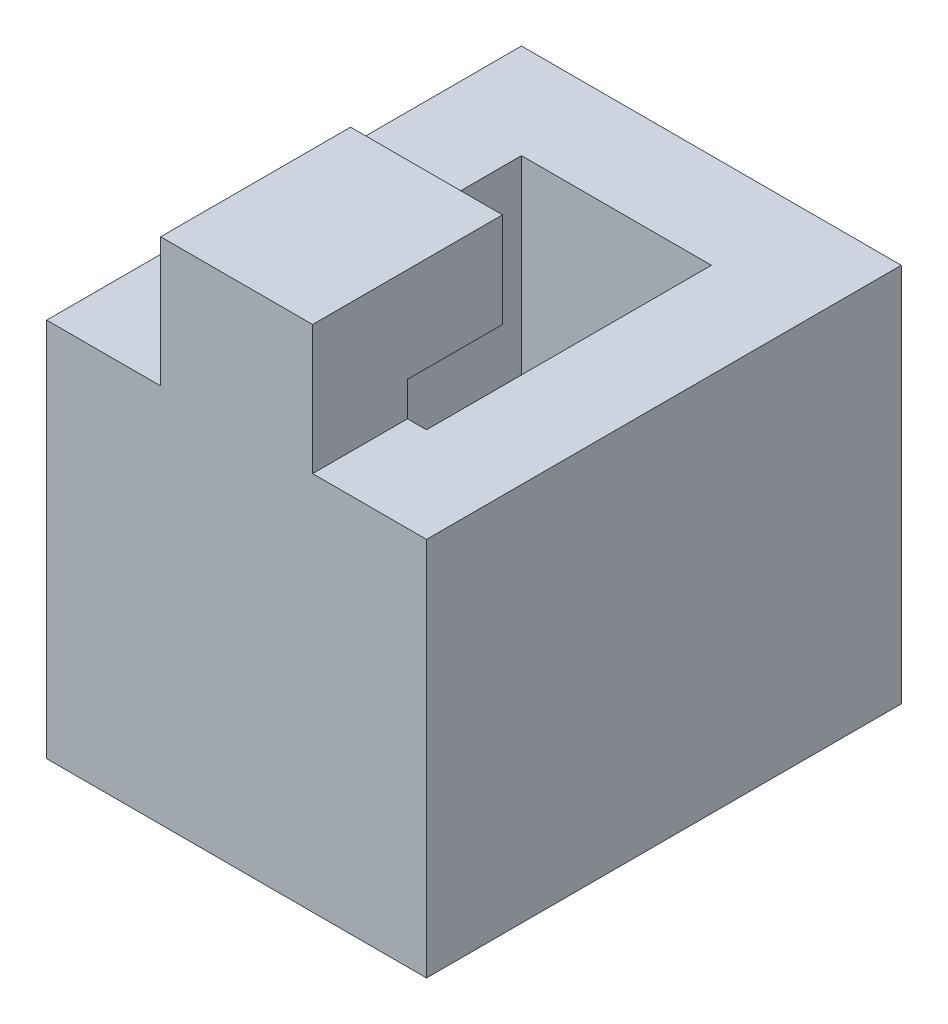
SolidWorks part; units mm, degrees
ref_plane "Front Plane" through (0, 0, 0) normal (0, 0, 1) x (1, 0, 0)
ref_plane "Top Plane" through (0, 0, 0) normal (0, 1, 0) x (1, 0, 0)
ref_plane "Right Plane" through (0, 0, 0) normal (1, 0, 0) x (0, 0, -1)
sketch "Sketch1" plane through (0, 0, 0) normal (0, 0, 1) x (1, 0, 0)
  line L0 (-4, 11.8) -> (4, 11.8)
  line L1 (-10, 10) -> (10, 10)
  line L2 (-10, 10) -> (-10, -10)
  line L3 (-10, -10) -> (10, -10)
  line L4 (10, 10) -> (10, -10)
  line L5 (-10, 10) -> (10, -10) construction
  line L6 (-10, -10) -> (10, 10) construction
  line L7 (-4, 16.8) -> (4, 16.8)
  line L8 (-4, 16.8) -> (-4, 10)
  line L9 (-4, 10) -> (4, 10)
  line L10 (4, 16.8) -> (4, 10)
  line L11 (-4, 16.8) -> (4, 10) construction
  line L12 (-4, 10) -> (4, 16.8) construction
  line L13 (5, 10) -> (-5, 10)
  line L14 (5, 10) -> (5, -10)
  line L15 (5, -10) -> (-5, -10)
  line L16 (-5, 10) -> (-5, -10)
  point P0 (0, 0)
  point P6 (0, 13.4)
  dimension "D1" = 20
  dimension "D2" = 20
  dimension "D3" = 8
  dimension "D4" = 6.8
  dimension "D5" = 5
  dimension "D6" = 5
  dimension "D7" = 1.8
extrude "Boss-Extrude1" add sketch "Sketch1" along normal blind 5 contours L16 L1 L2 L3 | L1 L16 L3 L14 | L1 L14 L3 L4 region at (0, 0, 0) region at (-7.5, 0, 0) region at (7.5, 0, 0)
hole_wizard "#4 (0.209) Diameter Hole1" positions "Sketch2" profile "Sketch3" hole size "#4" standard "ANSI Inch" end condition through all
sketch "Sketch2" plane through (0, 0, 5) normal (0, 0, 1) x (1, 0, 0)
  point P0 (0, 0)
sketch "Sketch3" plane through (0, 0, 5) normal (1, 0, 0) x (0, -1, 0)
  line L0 (0, 0) -> (0, 5)
  line L1 (0, 5) -> (2.6543, 5)
  line L2 (2.6543, 5) -> (2.6543, 0)
  line L5 (2.6543, 0) -> (0, 0)
  line L11 (0, -6.35) -> (0, 107.95) construction
  dimension "Thru Hole Dia." = 5.3086
  dimension "Thru Hole Depth" = 5
extrude "Boss-Extrude5" add sketch "Sketch1<5>" along normal blind 15 from surface contours L16 L1 L2 L3 | L1 L14 L3 L4 region at (-7.5, 0, 0) region at (7.5, 0, 0) starting at face at (2.6543, 0, 5)
sketch "Sketch1<5>" plane through (0, 0, 0) normal (0, 0, 1) x (1, 0, 0) same geometry as "Sketch1"
extrude "Boss-Extrude6" add sketch "Sketch1<6>" along normal blind 5 from surface contours L16 L1 L2 L3 | L1 L16 L3 L14 | L1 L14 L3 L4 region at (0, 0, 0) region at (-7.5, 0, 0) region at (7.5, 0, 0) starting at face at (-7.5, 0, 20)
sketch "Sketch1<6>" plane through (0, 0, 0) normal (0, 0, 1) x (1, 0, 0) same geometry as "Sketch1"
extrude "Boss-Extrude7" add sketch "Sketch1<7>" against normal blind 5 from surface contours L10 L8 L1 region at (0, 10.9, 0) starting at face at (0, 0, 25)
sketch "Sketch1<7>" plane through (0, 0, 0) normal (0, 0, 1) x (1, 0, 0) same geometry as "Sketch1"
extrude "Boss-Extrude8" add sketch "Sketch1<8>" against normal blind 10 from surface contours L10 L7 L8 L0 region at (0, 14.3, 0) starting at face at (0, 5.45, 25)
sketch "Sketch1<8>" plane through (0, 0, 0) normal (0, 0, 1) x (1, 0, 0) same geometry as "Sketch1"
